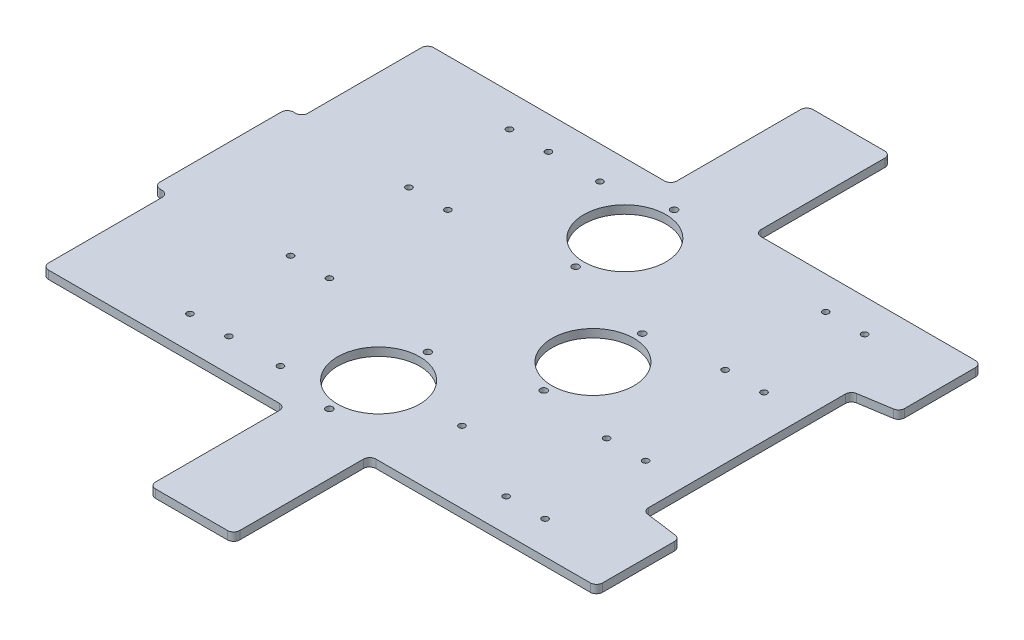
SolidWorks part; units mm, degrees
ref_plane "Front Plane" through (0, 0, 0) normal (0, 0, 1) x (1, 0, 0)
ref_plane "Top Plane" through (0, 0, 0) normal (0, 1, 0) x (1, 0, 0)
ref_plane "Right Plane" through (0, 0, 0) normal (1, 0, 0) x (0, 0, -1)
sketch "Sketch1" plane through (0, 0, 0) normal (0, 1, 0) x (1, 0, 0)
  line L4 (187.6801, 0) -> (-187.9931, 0) construction
  line L13 (92.4587, 93.85) -> (92.4587, 53.8038)
  line L14 (92.4587, 53.8038) -> (71.9148, 50.55)
  line L15 (92.5282, -53.3294) -> (71.9148, -50.55)
  line L16 (92.4587, -93.85) -> (92.5282, -53.3294)
  line L17 (71.9148, 50.55) -> (71.9148, -50.55)
  line L18 (-59.0413, 93.85) -> (-59.0413, 160.15)
  line L19 (-59.0413, 160.15) -> (-18.0413, 160.15)
  line L20 (-18.0413, 160.15) -> (-18.0413, 93.85)
  line L21 (-59.0413, 93.85) -> (-177.5413, 93.85)
  line L22 (-18.0413, 93.85) -> (92.4587, 93.85)
  line L23 (-18.0413, -93.85) -> (92.4587, -93.85)
  line L24 (-18.0413, -160.15) -> (-18.0413, -93.85)
  line L25 (-59.0413, -160.15) -> (-18.0413, -160.15)
  line L26 (-59.0413, -93.85) -> (-59.0413, -160.15)
  line L27 (-59.0413, -93.85) -> (-177.5413, -93.85)
  line L31 (-177.5413, 93.85) -> (-177.5413, 34.2746)
  line L32 (-177.5413, 34.2746) -> (-177.5413, 32.5)
  line L33 (-184.5413, -32.5) -> (-184.5413, 32.5)
  line L34 (-184.5413, 32.5) -> (-177.5413, 32.5)
  line L35 (-184.5413, -32.5) -> (-177.5413, -32.5)
  line L36 (-177.5413, -32.5) -> (-177.5413, -93.85)
  circle A0 centre (-47.5413, 60) radius 20
  circle A1 centre (-3.0852, 0) radius 20
  circle A2 centre (-47.5413, -60) radius 20
  circle A3 centre (-77.5413, 77.85) radius 1.5
  circle A4 centre (-121.6213, 28.85) radius 1.5
  circle A5 centre (-102.6513, 28.85) radius 1.5
  circle A6 centre (-121.6213, -28.85) radius 1.5
  circle A7 centre (-102.6513, -28.85) radius 1.5
  circle A8 centre (-77.5413, -77.85) radius 1.5
  circle A10 centre (32.4587, 77.85) radius 1.5
  circle A11 centre (-8.0852, -58.85) radius 1.5
  circle A12 centre (32.4587, -77.85) radius 1.5
  circle A14 centre (-121.6213, -77.85) radius 1.5
  circle A15 centre (-102.6513, -77.85) radius 1.5
  circle A16 centre (51.4287, -77.85) radius 1.5
  circle A17 centre (32.4448, -28.85) radius 1.5
  circle A18 centre (51.4148, -28.85) radius 1.5
  circle A19 centre (-121.6213, 77.85) radius 1.5
  circle A20 centre (-102.6513, 77.85) radius 1.5
  circle A21 centre (51.4148, 28.85) radius 1.5
  circle A22 centre (32.4448, 28.85) radius 1.5
  circle A23 centre (51.4287, 77.85) radius 1.5
  circle A24 centre (-47.5413, -84) radius 1.65
  circle A25 centre (-47.5413, -36) radius 1.65
  circle A26 centre (-3.0852, -24) radius 1.65
  circle A27 centre (-3.0852, 24) radius 1.65
  circle A28 centre (-47.5413, 36) radius 1.65
  circle A29 centre (-47.5413, 84) radius 1.65
  point P37 (-184.5413, 0)
  dimension "D12" = 40
  dimension "D13" = 40
  dimension "D14" = 100.15
  dimension "D16" = 75
  dimension "D17" = 93.85
  dimension "D18" = 3
  dimension "D19" = 16
  dimension "D20" = 100
  dimension "D21" = 16
  dimension "D22" = 65
  dimension "D23" = 81.89
  dimension "D24" = 60.0274
  dimension "D25" = 16
  dimension "D26" = 60
  dimension "D27" = 35
  dimension "D28" = 80
  dimension "D30" = 18.97
  dimension "D31" = 65
  dimension "D32" = 62.92
  dimension "D33" = 3
  dimension "D34" = 3
  dimension "D35" = 3
  dimension "D37" = 3
  dimension "D40" = 3
  dimension "D41" = 3
  dimension "D44" = 49
  dimension "D45" = 18.97
  dimension "D47" = 3
  dimension "D48" = 3
  dimension "D49" = 3
  dimension "D50" = 16
  dimension "D52" = 20.5
  dimension "D53" = 3.3
  dimension "D54" = 3.3
  dimension "D55" = 3.3
  dimension "D56" = 3.3
  dimension "D57" = 3.3
  dimension "D58" = 3.3
  dimension "D43" = 18.97
  dimension "D1" = 187.7
  dimension "D2" = 270
  dimension "D3" = 20.8
  dimension "D4" = 99
  dimension "D5" = 101.1
  dimension "D6" = 20.8
  dimension "D7" = 66.3
  dimension "D8" = 41
  dimension "D9" = 110.5
  dimension "D10" = 32.5
  dimension "D11" = 7
  dimension "D15" = 130
  dimension "D29" = 177.5413
  dimension "D38" = 49
  dimension "D39" = 49
  dimension "D42" = 18.97
extrude "Boss-Extrude2" add sketch "Sketch1" along normal blind 4
fillet "Fillet1" radius 3 20 edges at (-177.5413, 2, -93.85) (-184.5413, 2, -32.5) (-177.5413, 2, -32.5) (-184.5413, 2, 32.5) (-177.5413, 2, 32.5) (-177.5413, 2, 93.85) (-59.0413, 2, 93.85) (-59.0413, 2, 160.15) (-18.0413, 2, 160.15) (-18.0413, 2, 93.85) (92.4587, 2, 93.85) (92.5282, 2, 53.3294) (71.9148, 2, 50.55) (71.9148, 2, -50.55) (92.4587, 2, -53.8038) (92.4587, 2, -93.85) (-59.0413, 2, -93.85) (-18.0413, 2, -93.85) (-18.0413, 2, -160.15) (-59.0413, 2, -160.15)
